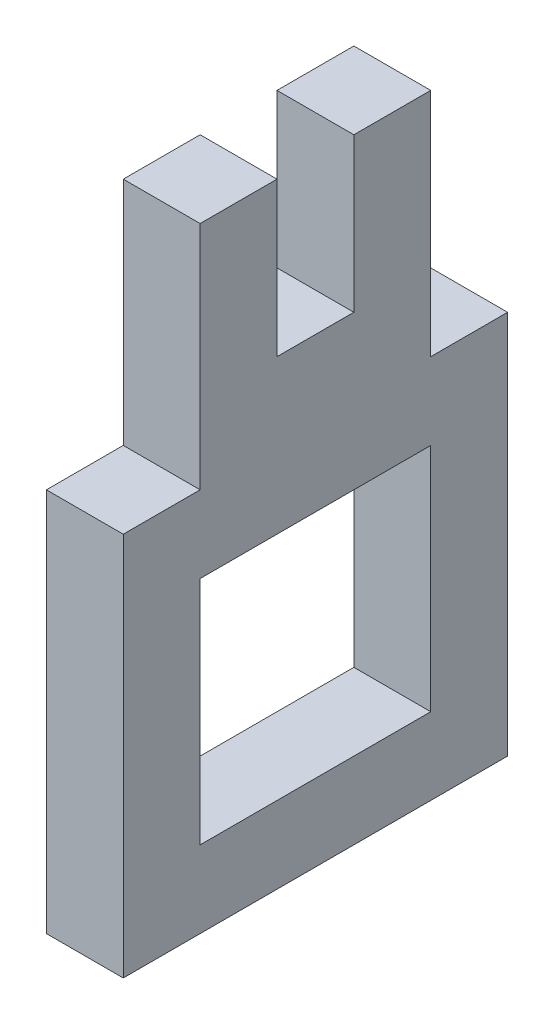
SolidWorks part; units mm, degrees
material "Balsa"
ref_plane "Front Plane" through (0, 0, 0) normal (0, 0, 1) x (1, 0, 0)
ref_plane "Top Plane" through (0, 0, 0) normal (0, 1, 0) x (1, 0, 0)
ref_plane "Right Plane" through (0, 0, 0) normal (1, 0, 0) x (0, 0, -1)
sketch "Sketch2" plane through (0, 0, 0) normal (1, 0, 0) x (0, 0, -1)
  line L2 (12.7, 50.8) -> (12.7, 38.1)
  line L3 (12.7, 38.1) -> (19.05, 38.1)
  line L4 (19.05, 38.1) -> (19.05, 50.8)
  line L5 (19.05, 50.8) -> (25.4, 50.8)
  line L7 (31.75, 0) -> (0, 0)
  line L9 (6.35, 6.35) -> (25.4, 6.35)
  line L10 (6.35, 6.35) -> (6.35, 25.4)
  line L11 (6.35, 25.4) -> (25.4, 25.4)
  line L12 (25.4, 6.35) -> (25.4, 25.4)
  line L16 (25.4, 50.8) -> (25.4, 31.75)
  line L17 (25.4, 31.75) -> (31.75, 31.75)
  line L18 (31.75, 31.75) -> (31.75, 0)
  line L20 (6.35, 31.75) -> (0, 31.75)
  line L21 (0, 31.75) -> (0, 0)
  line L22 (12.7, 50.8) -> (6.35, 50.8)
  line L23 (6.35, 50.8) -> (6.35, 31.75)
  point P1 (17.0528, 52.1155)
  point P13 (15.875, 38.1)
  point P16 (15.875, 0)
  point P18 (0, 0)
  point P20 (0, 0)
  point P21 (19.05, 53.6331)
  point P22 (12.7, 53.1348)
  point P23 (12.7, 38.1)
  dimension "D1" = 6.35
  dimension "D2" = 19.05
  dimension "D3" = 19.05
  dimension "D4" = 6.35
  dimension "D7" = 12.7
  dimension "D5" = 6.35
  dimension "D6" = 6.35
  dimension "D8" = 6.35
  dimension "D9" = 6.35
  dimension "D10" = 6.35
  dimension "D11" = 25.4
extrude "Boss-Extrude1" add sketch "Sketch2" along normal blind 6.35
equation "\"D2@Sketch2\"=\"D3@Sketch2\""
